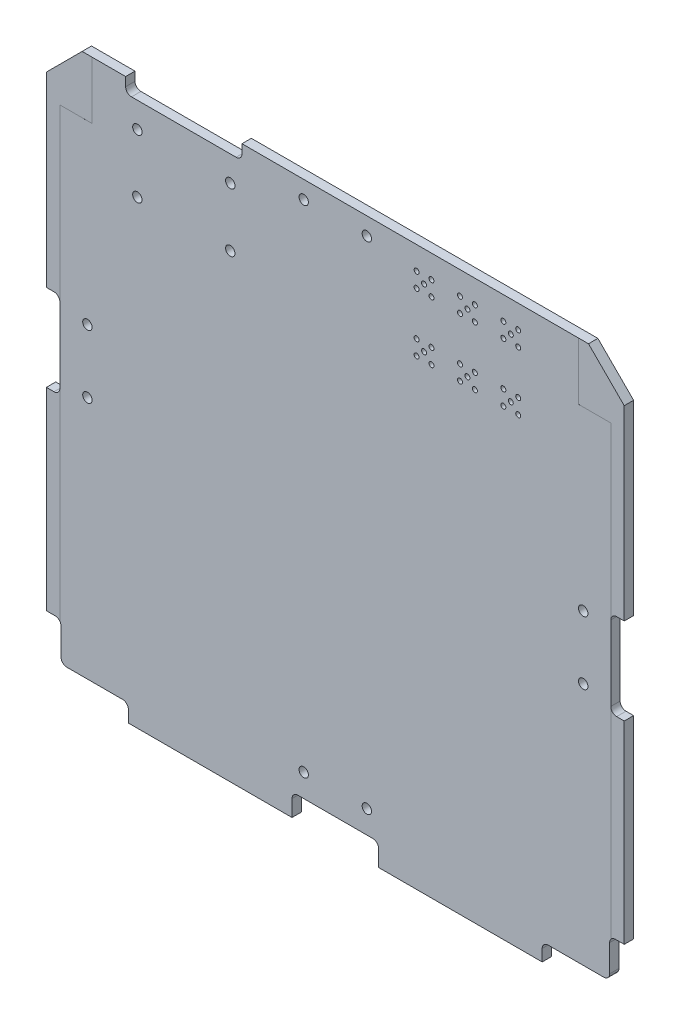
SolidWorks part; units mm, degrees
material "Oshpark board"
ref_plane "Front Plane" through (0, 0, 0) normal (0, 0, 1) x (1, 0, 0)
ref_plane "Top Plane" through (0, 0, 0) normal (0, 1, 0) x (1, 0, 0)
ref_plane "Right Plane" through (0, 0, 0) normal (1, 0, 0) x (0, 0, -1)
ref_plane "Plane4" through (0, 0, -0.0125) normal (0, 0, -1) x (-1, 0, 0)
sketch "Sketch1" plane through (0, 0, -0.0125) normal (0, 0, -1) x (-1, 0, 0)
  line L0 (35.3, -50) -> (35.3, -48)
  line L1 (36.3, -47) -> (45.8, -47)
  line L2 (46.8, -46) -> (46.8, -41.4)
  line L3 (47.8, -40.4) -> (49.3, -40.4)
  line L4 (49.3, -40.4) -> (49.3, 39.2)
  line L5 (49.3, 39.2) -> (43.2, 45.3)
  line L6 (43.2, 45.3) -> (35.5, 45.3)
  line L7 (35.5, 45.3) -> (35.5, 43.8) construction
  line L8 (34.5, 42.8) -> (4.5, 42.8) construction
  line L9 (3.5, 43.8) -> (3.5, 45.3) construction
  line L10 (3.5, 45.3) -> (-43.2, 45.3)
  line L11 (-43.2, 45.3) -> (-49.3, 39.2)
  line L12 (-49.3, 39.2) -> (-49.3, -40.4)
  line L13 (-49.3, -40.4) -> (-47.8, -40.4)
  line L14 (-46.8, -41.4) -> (-46.8, -46)
  line L15 (-45.8, -47) -> (-36.3, -47)
  line L16 (-35.3, -48) -> (-35.3, -50)
  line L17 (-35.3, -50) -> (35.3, -50)
  line L18 (0, -50) -> (0, 45.3) construction
  line L19 (19.5, 42.8) -> (19.5, 25.5258) construction
  line L20 (-13.87, 41.37) -> (-16.41, 38.83) construction
  line L21 (-21.27, 41.37) -> (-23.81, 38.83) construction
  line L22 (-28.67, 41.37) -> (-31.21, 38.83) construction
  line L23 (35.5, 45.3) -> (3.5, 45.3)
  arc A0 (35.3, -48) -> (36.3, -47) centre (36.3, -48) cw
  arc A1 (45.8, -47) -> (46.8, -46) centre (45.8, -46) ccw
  arc A2 (46.8, -41.4) -> (47.8, -40.4) centre (47.8, -41.4) cw
  arc A3 (35.5, 43.8) -> (34.5, 42.8) centre (34.5, 43.8) cw construction
  arc A4 (4.5, 42.8) -> (3.5, 43.8) centre (4.5, 43.8) cw construction
  arc A5 (-47.8, -40.4) -> (-46.8, -41.4) centre (-47.8, -41.4) cw
  arc A6 (-46.8, -46) -> (-45.8, -47) centre (-45.8, -46) ccw
  arc A7 (-36.3, -47) -> (-35.3, -48) centre (-36.3, -48) cw
  circle A8 centre (-21.27, 41.37) radius 0.425
  circle A9 centre (-23.81, 41.37) radius 0.425
  circle A10 centre (-22.54, 40.1) radius 0.425
  circle A11 centre (-13.87, 41.37) radius 0.425
  circle A12 centre (-23.81, 38.83) radius 0.425
  circle A13 centre (-16.41, 41.37) radius 0.425
  circle A14 centre (-15.14, 40.1) radius 0.425
  circle A15 centre (-21.27, 38.83) radius 0.425
  circle A16 centre (-28.67, 41.37) radius 0.425
  circle A17 centre (-31.21, 41.37) radius 0.425
  circle A18 centre (-16.41, 38.83) radius 0.425
  circle A19 centre (-29.94, 40.1) radius 0.425
  circle A20 centre (-31.21, 38.83) radius 0.425
  circle A21 centre (-28.67, 38.83) radius 0.425
  circle A22 centre (33.775, 38.54) radius 0.8 construction
  circle A23 centre (5.225, 38.54) radius 0.8 construction
  circle A24 centre (-13.87, 38.83) radius 0.425
  point P35 (-15.14, 40.1)
  dimension "D7" = 2.5
  dimension "D8" = 1.6
  dimension "D9" = 14.275
  dimension "D10" = 4.26
  dimension "D11" = 1
  dimension "D12" = 1
  dimension "D13" = 1
  dimension "D14" = 1
  dimension "D15" = 1
  dimension "D16" = 1
  dimension "D17" = 1
  dimension "D18" = 1
  dimension "D26" = 0.85
  dimension "D1" = 98.6
  dimension "D2" = 95.3
  dimension "D3" = 14
  dimension "D4" = 9.6
  dimension "D5" = 2.5
  dimension "D6" = 3
  dimension "D19" = 14
  dimension "D20" = 2.5
  dimension "D21" = 6.1
  dimension "D22" = 6.1
  dimension "D23" = 32
  dimension "D24" = 2.54
  dimension "D25" = 2.54
  dimension "D28" = 7.4
  dimension "D29" = 3.93
  dimension "D30" = 35.43
  dimension "D31" = 45
  dimension "D32" = 45
  dimension "D33" = 29.8
  dimension "D34" = 50
  dimension "D27" = 3
extrude "Boss-Extrude1" add sketch "Sketch1" against normal blind 1.6
sketch "thermalContacts_lower" plane through (0, 0, -0.0125) normal (0, 0, -1) x (-1, 0, 0)
  line L0 (47, 35.5) -> (47, -41.5) construction
  line L1 (41.5, 35.5) -> (41.5, 41.5) construction
  line L2 (41.5, 35.5) -> (47, 35.5) construction
  line L3 (47, 35.5) -> (47, -41.5)
  line L4 (41.5, 35.5) -> (41.5, 41.5)
  line L5 (41.5, 35.5) -> (47, 35.5)
  line L6 (-47, 35.5) -> (-47, -41.5) construction
  line L7 (-41.5, 35.5) -> (-47, 35.5) construction
  line L8 (-41.5, 35.5) -> (-41.5, 41.5) construction
  line L9 (-47, 35.5) -> (-47, -41.5)
  line L10 (-41.5, 35.5) -> (-47, 35.5)
  line L11 (-41.5, 35.5) -> (-41.5, 41.5)
  line L12 (-41.5, 41.5) -> (-41.5, 47) construction
  line L13 (-41.5, 41.5) -> (-49.5, 41.5) construction
  line L14 (-41.5, 41.5) -> (-41.5, 47)
  line L15 (-41.5, 41.5) -> (-49.5, 41.5) construction
  line L16 (41.5, 41.5) -> (41.5, 47) construction
  line L17 (41.5, 41.5) -> (49.5, 41.5) construction
  line L18 (41.5, 41.5) -> (41.5, 47)
  line L19 (41.5, 41.5) -> (49.5, 41.5) construction
  line L20 (47, -41.5) -> (59.8273, -41.5)
  line L21 (59.8273, -41.5) -> (59.8273, 47)
  line L22 (-56.1922, 47) -> (-41.5, 47)
  line L23 (41.5, 47) -> (59.8273, 47)
  line L24 (-56.1922, 47) -> (-56.1922, -41.5)
  line L25 (-47, -41.5) -> (-56.1922, -41.5)
sketch "thermalContacts_upper" plane through (0, 0, 1.5875) normal (0, 0, 1) x (1, 0, 0)
  line L3 (-47, 35.5) -> (-47, -41.5)
  line L4 (-41.5, 35.5) -> (-41.5, 41.5)
  line L5 (-41.5, 35.5) -> (-47, 35.5)
  line L9 (47, 35.5) -> (47, -41.5)
  line L10 (41.5, 35.5) -> (47, 35.5)
  line L11 (41.5, 35.5) -> (41.5, 41.5)
  line L14 (41.5, 41.5) -> (41.5, 47)
  line L15 (41.5, 41.5) -> (49.5, 41.5) construction
  line L18 (-41.5, 41.5) -> (-41.5, 47)
  line L19 (-41.5, 41.5) -> (-49.5, 41.5) construction
  line L20 (47, -41.5) -> (59.8273, -41.5)
  line L21 (59.8273, -41.5) -> (59.8273, 47)
  line L22 (59.8273, 47) -> (41.5, 47)
  line L23 (-41.5, 47) -> (-56.1922, 47)
  line L24 (-56.1922, 47) -> (-56.1922, -41.5)
  line L25 (-56.1922, -41.5) -> (-47, -41.5)
pattern_linear "LPattern2" count 2 spacing 10 along (0, -1, 0) of face at (14.295, 41.37, 1.5875) of face at (14.295, 38.83, 1.5875) of face at (15.565, 40.1, 1.5875) of face at (16.835, 38.83, 1.5875) of face at (21.695, 41.37, 1.5875) of face at (21.695, 38.83, 1.5875) of face at (22.965, 40.1, 1.5875) of face at (24.235, 38.83, 1.5875) of face at (24.235, 41.37, 1.5875) of face at (16.835, 41.37, 1.5875) of face at (29.095, 41.37, 1.5875) of face at (29.095, 38.83, 1.5875) of face at (30.365, 40.1, 1.5875) of face at (31.635, 38.83, 1.5875) of face at (31.635, 41.37, 1.5875)
extrude "slotFootprints_REF" cut sketch "thermalContacts_lower" against normal blind 0.0001
extrude "slotFootprints" cut sketch "thermalContacts_upper" against normal blind 0.0001
sketch "Sketch2" plane through (0, 0, 1.5875) normal (0, 0, 1) x (1, 0, 0)
  line L1 (-41.5, 45.3) -> (41.5, 45.3) construction
  line L2 (-49.3, -40.4) -> (-49.3, 39.2) construction
  line L3 (-35.775, 45.3) -> (-35.775, 43.8)
  line L4 (-41.5, 45.3) -> (41.5, 45.3) construction
  line L5 (-34.775, 42.8) -> (-16.925, 42.8)
  line L6 (-15.925, 43.8) -> (-15.925, 45.3)
  line L7 (-15.925, 45.3) -> (-35.775, 45.3)
  arc A1 (-16.925, 42.8) -> (-15.925, 43.8) centre (-16.925, 43.8) ccw
  arc A2 (-35.775, 43.8) -> (-34.775, 42.8) centre (-34.775, 43.8) ccw
  circle A3 centre (-33.775, 38.4723) radius 0.8
  circle A4 centre (-17.925, 38.4723) radius 0.8
  circle A5 centre (-17.925, 28.4723) radius 0.8
  circle A6 centre (-33.775, 28.4723) radius 0.8
  dimension "D2" = 1.6
  dimension "D5" = 1
  dimension "D1" = 15.85
  dimension "D3" = 6.8277
  dimension "D4" = 15.525
  dimension "D6" = 2
  dimension "D7" = 2
  dimension "D8" = 2.5
  dimension "D10" = 10
  dimension "D9" = 2
extrude "20pin_mounts" cut sketch "Sketch2" against normal through all
sketch "Sketch3" plane through (0, 0, -0.0125) normal (0, 0, -1) x (-1, 0, 0)
  line L0 (-49.3, -40.4) -> (-49.3, 39.2) construction
  line L1 (5.39, 42.3) -> (-5.38, 42.3) construction
  line L2 (42.3, -5.39) -> (42.3, 5.38) construction
  line L3 (15.925, 45.3) -> (-41.5, 45.3) construction
  line L4 (5.39, -42.3032) -> (-5.38, -42.3032) construction
  line L5 (-42.3, -5.39) -> (-42.3, 5.38) construction
  line L6 (41.5, 45.3) -> (35.775, 45.3) construction
  line L7 (42.3, -0.005) -> (-42.3, -0.005) construction
  line L8 (0.005, -42.3032) -> (0.005, 42.3) construction
  line L9 (49.3, -40.4) -> (49.3, 39.2) construction
  line L10 (-35.3, -50) -> (35.3, -50) construction
  line L11 (-42.3, -0.005) -> (-49.3, -0.005) construction
  line L12 (42.3, -0.005) -> (49.3, -0.005) construction
  line L13 (49.3, -40.4) -> (49.3, 39.2) construction
  line L14 (-49.3, 7.38) -> (-48, 7.38)
  line L15 (-47, 6.38) -> (-47, -6.39)
  line L16 (-48, -7.39) -> (-49.3, -7.39)
  line L17 (-49.3, -7.39) -> (-49.3, 7.38)
  line L18 (-49.3, -40.4) -> (-49.3, 39.2) construction
  line L19 (-47, 35.5) -> (-47, -40.8) construction
  line L20 (47, -40.8) -> (47, 35.5) construction
  line L21 (48, 7.38) -> (49.3, 7.38)
  line L22 (47, 6.38) -> (47, -6.39)
  line L23 (48, -7.39) -> (49.3, -7.39)
  line L24 (49.3, 7.38) -> (49.3, -7.39)
  line L26 (-6.38, -46.2032) -> (6.39, -46.2032)
  line L27 (-7.38, -47.2032) -> (-7.38, -50)
  line L28 (-7.38, -50) -> (7.39, -50)
  line L29 (7.39, -47.2032) -> (7.39, -50)
  arc A0 (-47, -6.39) -> (-48, -7.39) centre (-48, -6.39) cw
  arc A1 (-48, 7.38) -> (-47, 6.38) centre (-48, 6.38) cw
  circle A2 centre (5.39, 42.3) radius 0.8
  circle A3 centre (-5.38, 42.3) radius 0.8
  arc A4 (47, -6.39) -> (48, -7.39) centre (48, -6.39) ccw
  arc A5 (48, 7.38) -> (47, 6.38) centre (48, 6.38) ccw
  arc A6 (-6.38, -46.2032) -> (-7.38, -47.2032) centre (-6.38, -47.2032) ccw
  circle A7 centre (42.3, 5.38) radius 0.8
  circle A8 centre (42.3, -5.39) radius 0.8
  circle A9 centre (5.39, -42.3032) radius 0.8
  circle A10 centre (-5.38, -42.3032) radius 0.8
  circle A11 centre (-42.3, -5.39) radius 0.8
  circle A12 centre (-42.3, 5.38) radius 0.8
  arc A13 (6.39, -46.2032) -> (7.39, -47.2032) centre (6.39, -47.2032) cw
  point P16 (-47, -0.005)
  point P51 (47, -0.005)
  point P63 (0.005, -46.2032)
  dimension "D1" = 1.6
  dimension "D5" = 39.92
  dimension "D6" = 7
  dimension "D9" = 1
  dimension "D11" = 1
  dimension "D14" = 1
  dimension "D2" = 10.77
  dimension "D3" = 43.92
  dimension "D4" = 3
  dimension "D7" = 7.6968
  dimension "D8" = 2
  dimension "D10" = 2
  dimension "D12" = 3.9
  dimension "D13" = 2
extrude "12pin_mounts" cut sketch "Sketch3" against normal blind 10
